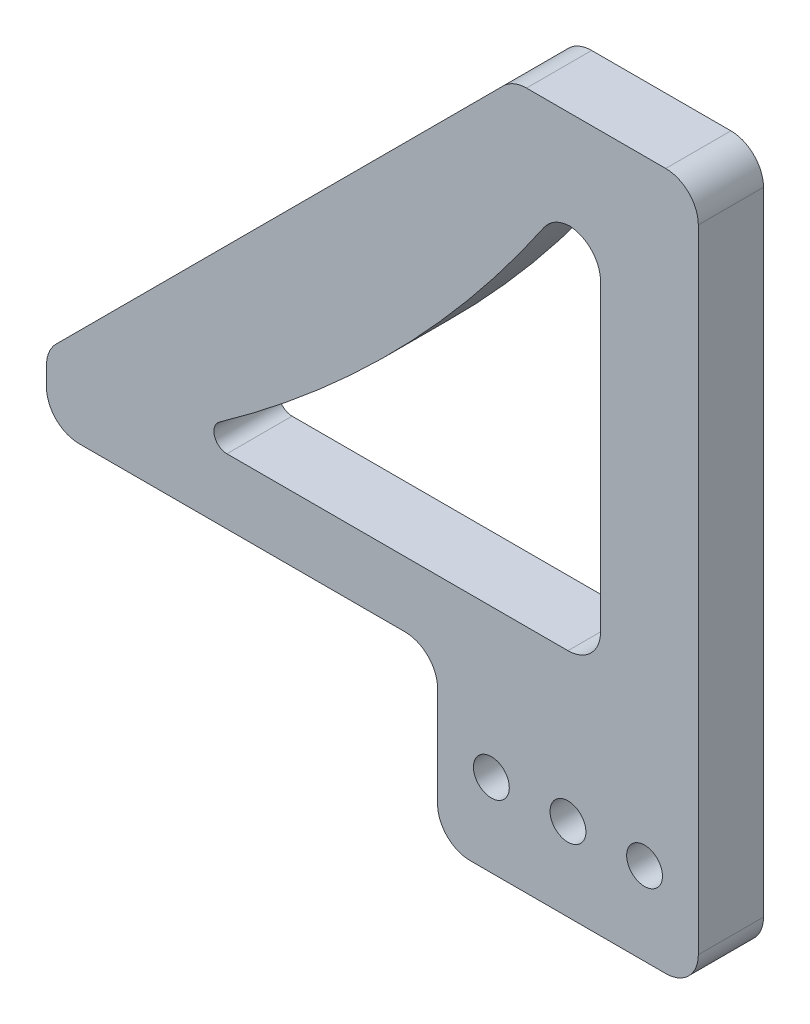
SolidWorks part; units mm, degrees
material "6061 Alloy"
ref_plane "Front" through (0, 0, 0) normal (0, 0, 1) x (1, 0, 0)
ref_plane "Top" through (0, 0, 0) normal (0, 1, 0) x (1, 0, 0)
ref_plane "Right" through (0, 0, 0) normal (1, 0, 0) x (0, 0, -1)
sketch "Sketch1" plane through (0, 0, 0) normal (0, 0, 1) x (1, 0, 0)
  line L0 (-60, 10) -> (11.5685, 81.5685)
  line L1 (11.5685, 81.5685) -> (40, 81.5685)
  line L2 (40, 81.5685) -> (40, -25.4)
  line L3 (40, -25.4) -> (0, -25.4)
  line L4 (0, -25.4) -> (0, 0)
  line L5 (0, 0) -> (-60, 0)
  line L6 (-60, 0) -> (-60, 10)
  line L7 (-38.7868, 10) -> (17.7817, 66.5685) construction
  line L8 (17.7817, 66.5685) -> (25, 66.5685)
  line L9 (25, 66.5685) -> (25, 10)
  line L10 (25, 10) -> (-38.7868, 10)
  line L11 (-71.4288, 85.35) -> (79.9478, 85.35) construction
  line L12 (-52.5613, 0) -> (69.8542, 0) construction
  line L13 (-52.5613, 0) -> (-52.5613, -25.4) construction
  line L14 (-52.5613, -25.4) -> (69.8542, -25.4) construction
  line L15 (69.8542, 0) -> (69.8542, -25.4) construction
  circle A0 centre (8.25, -12.7) radius 2.75
  circle A1 centre (20, -12.7) radius 2.75
  circle A2 centre (31.75, -12.7) radius 2.75
  arc A3 (17.7817, 66.5685) -> (-38.7868, 10) centre (-149.0666, 176.8483) cw
  point P23 (-52.5613, -12.7)
  point P25 (20, -25.4)
  dimension "D10" = 5.5
  dimension "D11" = 5.5
  dimension "D12" = 5.5
  dimension "D14" = 200
  dimension "D1" = 15
  dimension "D2" = 15
  dimension "D3" = 15
  dimension "D4" = 10
  dimension "D5" = 80
  dimension "D6" = 25.4
  dimension "D7" = 85.35
  dimension "D8" = 40
  dimension "D9" = 45
  dimension "D13" = 100
extrude "Boss-Extrude1" add sketch "Sketch1" along normal blind 10
fillet "Fillet1" radius 5 10 edges at (17.7817, 66.5685, 5) (25, 66.5685, 5) (25, 10, 5) (0, 0, 5) (-60, 0, 5) (-60, 10, 5) (0, -25.4, 5) (40, -25.4, 5) (40, 81.5685, 5) (11.5685, 81.5685, 5)
fillet "Fillet2" radius 2 1 edges at (-38.7868, 10, 5)
